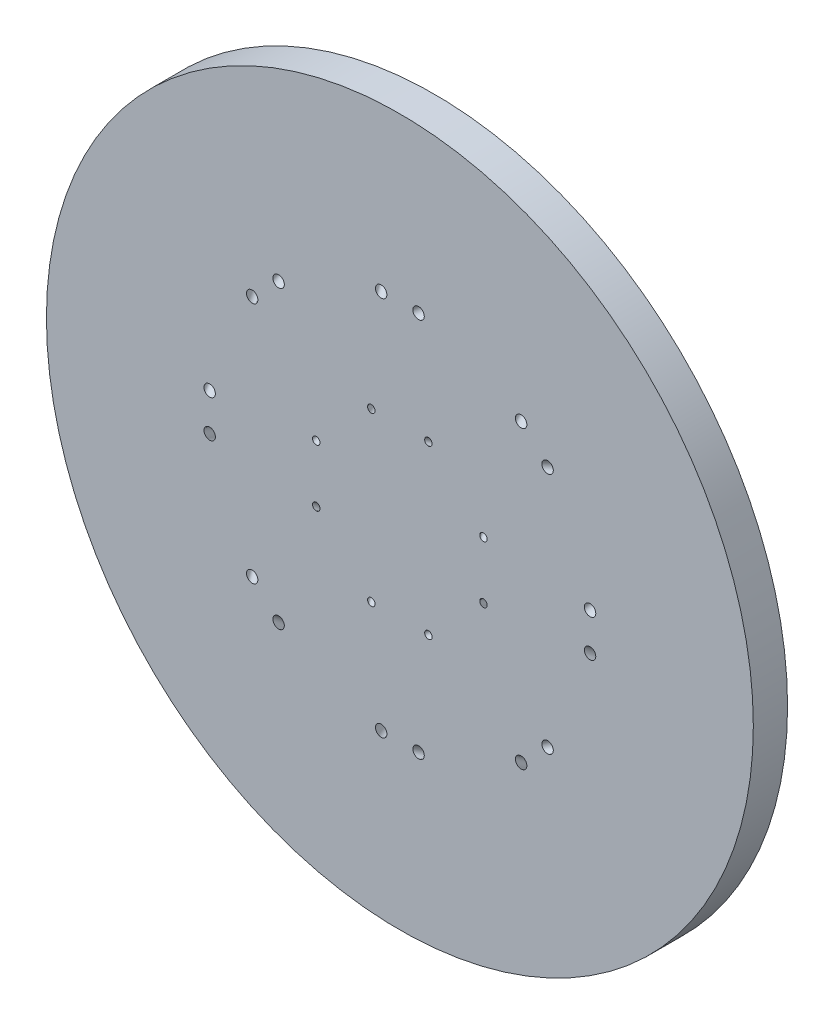
SolidWorks part; units mm, degrees
ref_plane "Front Plane" through (0, 0, 0) normal (0, 0, 1) x (1, 0, 0)
ref_plane "Top Plane" through (0, 0, 0) normal (0, 1, 0) x (1, 0, 0)
ref_plane "Right Plane" through (0, 0, 0) normal (1, 0, 0) x (0, 0, -1)
sketch "Sketch1" plane through (0, 0, 0) normal (0, 0, 1) x (1, 0, 0)
  circle A0 centre (0, 0) radius 38.1
  dimension "D1" = 76.2
extrude "Boss-Extrude1" add sketch "Sketch1" against normal blind 3.6912
sketch "Sketch2" plane through (0, 0, 0) normal (0, 0, 1) x (1, 0, 0)
  line L0 (0, 0) -> (0, 20.6) construction
  line L1 (0, 0) -> (20.6, 0) construction
  circle A0 centre (0, 0) radius 20.6 construction
  circle A1 centre (0, 0) radius 9.525 construction
  dimension "D1" = 41.2
  dimension "D2" = 19.05
sketch "Sketch4" plane through (0, 0, 0) normal (0, 0, 1) x (1, 0, 0)
  line L0 (-3.076, 9.0146) -> (3.076, 9.0146) construction
  line L1 (0, 0) -> (0, 20.6) construction
  line L3 (9.0146, 3.076) -> (9.0146, -3.076) construction
  line L4 (3.076, -9.0146) -> (-3.076, -9.0146) construction
  line L5 (-9.0146, -3.076) -> (-9.0146, 3.076) construction
  line L6 (-3.076, -9.0146) -> (3.076, -9.0146) construction
  line L8 (-9.0146, 3.076) -> (-9.0146, -3.076) construction
  circle A1 centre (9.0146, 3.076) radius 0.403
  circle A3 centre (-3.076, 9.0146) radius 0.403
  circle A4 centre (0, 0) radius 9.525 construction
  circle A5 centre (3.076, 9.0146) radius 0.403
  circle A6 centre (9.0146, -3.076) radius 0.403
  circle A7 centre (3.076, -9.0146) radius 0.403
  circle A8 centre (-3.076, -9.0146) radius 0.403
  circle A9 centre (-9.0146, -3.076) radius 0.403
  circle A10 centre (-9.0146, 3.076) radius 0.403
  point P6 (0, 9.0146)
  point P40 (0, 0)
  dimension "D1" = 0.806
  dimension "D2" = 0.806
  dimension "D3" = 6.152
  dimension "D4" = 4
sketch "Sketch5" plane through (0, 0, 0) normal (0, 0, 1) x (1, 0, 0)
  line L0 (-2.015, 20.5012) -> (2.015, 20.5012) construction
  line L1 (0, 0) -> (0, 20.6) construction
  line L2 (13.0717, 15.9214) -> (15.9214, 13.0717) construction
  line L3 (20.5012, -2.015) -> (20.5012, 2.015) construction
  line L4 (13.0717, -15.9214) -> (15.9214, -13.0717) construction
  line L5 (-2.015, -20.5012) -> (2.015, -20.5012) construction
  line L6 (-15.9214, -13.0717) -> (-13.0717, -15.9214) construction
  line L7 (-20.5012, 2.015) -> (-20.5012, -2.015) construction
  line L8 (-13.0717, 15.9214) -> (-15.9214, 13.0717) construction
  circle A0 centre (-2.015, 20.5012) radius 0.6152
  circle A1 centre (0, 0) radius 20.6 construction
  circle A2 centre (2.015, 20.5012) radius 0.6152
  circle A3 centre (13.0717, 15.9214) radius 0.6152
  circle A4 centre (15.9214, 13.0717) radius 0.6152
  circle A5 centre (20.5012, 2.015) radius 0.6152
  circle A6 centre (20.5012, -2.015) radius 0.6152
  circle A7 centre (15.9214, -13.0717) radius 0.6152
  circle A8 centre (13.0717, -15.9214) radius 0.6152
  circle A9 centre (2.015, -20.5012) radius 0.6152
  circle A10 centre (-2.015, -20.5012) radius 0.6152
  circle A11 centre (-13.0717, -15.9214) radius 0.6152
  circle A12 centre (-15.9214, -13.0717) radius 0.6152
  circle A13 centre (-20.5012, -2.015) radius 0.6152
  circle A14 centre (-20.5012, 2.015) radius 0.6152
  circle A15 centre (-15.9214, 13.0717) radius 0.6152
  circle A16 centre (-13.0717, 15.9214) radius 0.6152
  point P6 (0, 20.5012)
  point P28 (0, 0)
  dimension "D1" = 1.2304
  dimension "D2" = 1.2304
  dimension "D3" = 4.03
  dimension "D4" = 8
ref_plane "Plane1" through (0, 17.9868, 6.725) normal (0, 0.9367, 0.3502) x (1, 0, 0)
ref_plane "Plane2" through (0, 7.909, -2.9571) normal (0, -0.9367, 0.3502) x (1, 0, 0)
ref_plane "Plane3" through (12.7186, 12.7186, 6.725) normal (0.6623, 0.6623, 0.3502) x (0.7071, -0.7071, 0)
ref_plane "Plane4" through (17.9868, 0, 6.725) normal (0.9367, 0, 0.3502) x (0, 1, 0)
ref_plane "Plane5" through (12.7186, -12.7186, 6.725) normal (0.6623, -0.6623, 0.3502) x (0.7071, 0.7071, 0)
ref_plane "Plane7" through (-7.909, 0, -2.9571) normal (0.9367, 0, 0.3502) x (0, -1, 0)
ref_plane "Plane8" through (0, -7.909, -2.9571) normal (0, 0.9367, 0.3502) x (-1, 0, 0)
ref_plane "Plane9" through (0, -7.909, -2.9571) normal (0, 0.9367, 0.3502) x (1, 0, 0)
ref_plane "Plane10" through (-12.7186, -12.7186, 6.725) normal (-0.6623, -0.6623, 0.3502) x (0.7071, -0.7071, 0)
ref_plane "Plane11" through (-7.909, 0, 2.9571) normal (-0.9367, 0, 0.3502) x (0, 1, 0)
ref_plane "Plane12" through (7.909, 0, -2.9571) normal (-0.9367, 0, 0.3502) x (0, -1, 0)
ref_plane "Plane13" through (-12.7186, 12.7186, 6.725) normal (-0.6623, 0.6623, 0.3502) x (-0.7071, -0.7071, 0)
ref_plane "Plane14" through (0, -17.9868, 6.725) normal (0, -0.9367, 0.3502) x (1, 0, 0)
sketch "Sketch6" plane through (12.7186, -12.7186, 6.725) normal (0.6623, -0.6623, 0.3502) x (0.7071, 0.7071, 0)
  line L0 (-2.015, -7.1797) -> (2.015, -7.1797)
  line L1 (0, -7.1797) -> (0, -3.6896) construction
  line L2 (-2.015, -7.1797) -> (0, -3.6896)
  line L3 (0, -3.6896) -> (2.015, -7.1797)
  dimension "D1" = 60
sketch "Sketch7" plane through (17.9868, 0, 6.725) normal (0.9367, 0, 0.3502) x (0, 1, 0)
  line L0 (-2.015, -7.1797) -> (2.015, -7.1797)
  line L1 (0, -7.1797) -> (0, -3.6896) construction
  line L2 (-2.015, -7.1797) -> (0, -3.6896)
  line L3 (0, -3.6896) -> (2.015, -7.1797)
  dimension "D1" = 60
sketch "Sketch8" plane through (12.7186, 12.7186, 6.725) normal (0.6623, 0.6623, 0.3502) x (0.7071, -0.7071, 0)
  line L0 (-2.015, 7.1797) -> (2.015, 7.1797)
  line L1 (0, 7.1797) -> (0, 3.6896) construction
  line L3 (-2.015, 7.1797) -> (0, 3.6896)
  line L4 (0, 3.6896) -> (2.015, 7.1797)
  dimension "D1" = 60
sketch "Sketch9" plane through (0, 17.9868, 6.725) normal (0, 0.9367, 0.3502) x (1, 0, 0)
  line L0 (-2.015, 7.1797) -> (2.015, 7.1797)
  line L1 (0, 7.1797) -> (0, 3.6896) construction
  line L2 (0, 0) -> (0, 7.2143) construction
  line L3 (-2.015, 7.1797) -> (0, 3.6896)
  line L4 (0, 3.6896) -> (2.015, 7.1797)
  dimension "D1" = 60
sketch "Sketch10" plane through (0, 7.909, -2.9571) normal (0, -0.9367, 0.3502) x (1, 0, 0)
  line L0 (-3.076, 3.157) -> (3.076, 3.157)
  line L1 (0, 3.157) -> (0, 8.4848) construction
  line L2 (0, 0) -> (0, 7.2143) construction
  line L3 (0, 8.4848) -> (-3.076, 3.157)
  line L4 (0, 8.4848) -> (3.076, 3.157)
  dimension "D1" = 60
sketch "Sketch12" plane through (-7.909, 0, -2.9571) normal (0.9367, 0, 0.3502) x (0, -1, 0)
  line L0 (-3.076, -3.157) -> (3.076, -3.157)
  line L1 (0, -3.157) -> (0, -8.4848) construction
  line L2 (-3.076, -3.157) -> (0, -8.4848)
  line L3 (0, -8.4848) -> (3.076, -3.157)
  dimension "D1" = 60
sketch "Sketch14" plane through (0, -7.909, -2.9571) normal (0, 0.9367, 0.3502) x (1, 0, 0)
  line L0 (-3.076, -3.157) -> (3.076, -3.157)
  line L1 (0, -3.157) -> (0, -8.4848) construction
  line L2 (-3.076, -3.157) -> (0, -8.4848)
  line L3 (0, -8.4848) -> (3.076, -3.157)
  dimension "D1" = 60
ref_plane "Plane15" through (-17.9868, 0, 6.725) normal (-0.9367, 0, 0.3502) x (0, -1, 0)
sketch "Sketch16" plane through (7.909, 0, -2.9571) normal (-0.9367, 0, 0.3502) x (0, -1, 0)
  line L0 (-3.076, 3.157) -> (3.076, 3.157)
  line L4 (-3.076, 3.157) -> (0, 8.4848)
  line L5 (0, 8.4848) -> (3.076, 3.157)
  line L6 (0, 3.157) -> (0, 8.4848) construction
  dimension "D2" = 60
sketch "Sketch17" plane through (0, -7.909, -2.9571) normal (0, 0.9367, 0.3502) x (-1, 0, 0)
  line L0 (-3.076, 3.157) -> (3.076, 3.157)
  line L1 (0, 3.157) -> (0, 8.4848) construction
  line L3 (-3.076, 3.157) -> (0, 8.4848)
  line L4 (0, 8.4848) -> (3.076, 3.157)
  dimension "D1" = 60
sketch "Sketch18" plane through (0, 17.9868, 6.725) normal (0, 0.9367, 0.3502) x (1, 0, 0)
  line L0 (0, 10.3969) -> (0, -5.2208) construction
sketch "Sketch20" plane through (0, 7.909, -2.9571) normal (0, -0.9367, 0.3502) x (1, 0, 0)
  line L0 (0, 3.157) -> (0, 18.139) construction
sketch "Sketch21" plane through (-12.7186, -12.7186, 6.725) normal (-0.6623, -0.6623, 0.3502) x (0.7071, -0.7071, 0)
  line L0 (-2.015, -7.1797) -> (2.015, -7.1797)
  line L1 (2.015, -7.1797) -> (0, -3.6896)
  line L2 (0, -3.6896) -> (-2.015, -7.1797)
  line L3 (0, -7.1797) -> (0, -3.6896) construction
  dimension "D1" = 60
sketch "Sketch22" plane through (-12.7186, 12.7186, 6.725) normal (-0.6623, 0.6623, 0.3502) x (-0.7071, -0.7071, 0)
  line L0 (2.015, -7.1797) -> (-2.015, -7.1797)
  line L1 (-2.015, -7.1797) -> (0, -3.6896)
  line L2 (0, -3.6896) -> (2.015, -7.1797)
  line L3 (0, -7.1797) -> (0, -3.6896) construction
  dimension "D1" = 60
sketch "Sketch23" plane through (0, -17.9868, 6.725) normal (0, -0.9367, 0.3502) x (1, 0, 0)
  line L0 (-2.015, -7.1797) -> (2.015, -7.1797)
  line L1 (2.015, -7.1797) -> (0, -3.6896)
  line L2 (0, -3.6896) -> (-2.015, -7.1797)
  line L3 (0, -3.6896) -> (0, -7.1797) construction
  dimension "D1" = 60
sketch "Sketch24" plane through (-17.9868, 0, 6.725) normal (-0.9367, 0, 0.3502) x (0, -1, 0)
  line L0 (-2.015, -7.1797) -> (2.015, -7.1797)
  line L1 (2.015, -7.1797) -> (0, -3.6896)
  line L2 (0, -3.6896) -> (-2.015, -7.1797)
  line L3 (0, -3.6896) -> (0, -7.1797) construction
  dimension "D1" = 60
extrude "Cut-Extrude1" cut sketch "Sketch5" along direction (0.5, -0.3033, 0.8112) on the side against the normal up to surface (3.6912 mm away) contours A0 up to face at (38.1, 0, -3.6912)
extrude "Cut-Extrude2" cut sketch "Sketch5<3>" along direction (0.5, 0.3033, -0.8112) on the side against the normal up to surface (3.6912 mm away) contours A2 region at (2.015, 20.5012, 0) up to face at (-4.9032, 21.8293, -3.6912)
sketch "Sketch5<3>" plane through (0, 0, 0) normal (0, 0, 1) x (1, 0, 0) same geometry as "Sketch5"
extrude "Cut-Extrude3" cut sketch "Sketch5<4>" along direction (0.1391, -0.568, 0.8112) on the side against the normal up to surface (3.6912 mm away) contours A3 region at (13.0717, 15.9214, 0) up to face at (3.6772, 21.8293, -3.6912)
sketch "Sketch5<4>" plane through (0, 0, 0) normal (0, 0, 1) x (1, 0, 0) same geometry as "Sketch5"
extrude "Cut-Extrude4" cut sketch "Sketch5<5>" along direction (0.568, -0.1391, -0.8112) on the side against the normal up to surface (3.6912 mm away) contours A4 region at (15.9214, 13.0717, 0) up to face at (11.8258, 18.454, -3.6912)
sketch "Sketch5<5>" plane through (0, 0, 0) normal (0, 0, 1) x (1, 0, 0) same geometry as "Sketch5"
extrude "Cut-Extrude5" cut sketch "Sketch5<6>" along direction (-0.3033, 0.5, 0.8112) on the side against the normal up to surface (3.6912 mm away) contours A6 region at (20.5012, -2.015, 0) up to face at (17.893, 12.3868, -3.6912)
sketch "Sketch5<6>" plane through (0, 0, 0) normal (0, 0, 1) x (1, 0, 0) same geometry as "Sketch5"
extrude "Cut-Extrude6" cut sketch "Sketch5<7>" along direction (0.3033, 0.5, -0.8112) on the side against the normal up to surface (3.6912 mm away) contours A5 region at (20.5012, 2.015, 0) up to face at (21.2683, -4.3422, -3.6912)
sketch "Sketch5<7>" plane through (0, 0, 0) normal (0, 0, 1) x (1, 0, 0) same geometry as "Sketch5"
extrude "Cut-Extrude7" cut sketch "Sketch5<8>" along direction (0.1391, 0.568, 0.8112) on the side against the normal up to surface (3.6912 mm away) contours A8 region at (13.0717, -15.9214, 0) up to face at (21.2683, 4.2382, -3.6912)
sketch "Sketch5<8>" plane through (0, 0, 0) normal (0, 0, 1) x (1, 0, 0) same geometry as "Sketch5"
extrude "Cut-Extrude8" cut sketch "Sketch5<9>" along direction (0.568, 0.1391, -0.8112) on the side against the normal up to surface (3.6912 mm away) contours A7 region at (15.9214, -13.0717, 0) up to face at (11.8258, -18.5581, -3.6912)
sketch "Sketch5<9>" plane through (0, 0, 0) normal (0, 0, 1) x (1, 0, 0) same geometry as "Sketch5"
extrude "Cut-Extrude9" cut sketch "Sketch4" along direction (-0.5, -0.3033, -0.8112) on the side against the normal up to surface (3.6912 mm away) contours A3 region at (-3.076, 9.0146, 0) up to face at (17.893, -12.4908, -3.6912)
extrude "Cut-Extrude10" cut sketch "Sketch4<3>" along direction (0.5, -0.3033, -0.8112) on the side against the normal up to surface (3.6912 mm away) contours A5 region at (3.076, 9.0146, 0) up to face at (-5.7528, 7.6005, -3.6912)
sketch "Sketch4<3>" plane through (0, 0, 0) normal (0, 0, 1) x (1, 0, 0) same geometry as "Sketch4"
extrude "Cut-Extrude11" cut sketch "Sketch4<4>" along direction (0.5, -0.3033, 0.8112) on the side against the normal up to surface (3.6912 mm away) contours A8 region at (-3.076, -9.0146, 0) up to face at (4.9496, 7.6005, -3.6912)
sketch "Sketch4<4>" plane through (0, 0, 0) normal (0, 0, 1) x (1, 0, 0) same geometry as "Sketch4"
extrude "Cut-Extrude12" cut sketch "Sketch4<6>" along direction (0.5, 0.3033, -0.8112) on the side against the normal up to surface (3.6912 mm away) contours A7 region at (3.076, -9.0146, 0) up to face at (-5.7528, -7.6686, -3.6912)
sketch "Sketch4<6>" plane through (0, 0, 0) normal (0, 0, 1) x (1, 0, 0) same geometry as "Sketch4"
extrude "Cut-Extrude13" cut sketch "Sketch4<7>" along direction (-0.3033, -0.5, 0.8112) on the side against the normal up to surface (3.6912 mm away) contours A10 region at (-9.0146, 3.076, 0) up to face at (4.9496, -7.6686, -3.6912)
sketch "Sketch4<7>" plane through (0, 0, 0) normal (0, 0, 1) x (1, 0, 0) same geometry as "Sketch4"
extrude "Cut-Extrude14" cut sketch "Sketch4<8>" along direction (0.3033, -0.5, -0.8112) on the side against the normal up to surface (3.6912 mm away) contours A9 region at (-9.0146, -3.076, 0) up to face at (-8.0361, 5.3171, -3.6912)
sketch "Sketch4<8>" plane through (0, 0, 0) normal (0, 0, 1) x (1, 0, 0) same geometry as "Sketch4"
extrude "Cut-Extrude26" cut sketch "Sketch5<10>" along direction (-0.5, 0.3033, 0.8112) on the side against the normal up to surface (3.6912 mm away) contours A9 region at (2.015, -20.5012, 0) up to face at (-8.0361, -5.3853, -3.6912)
sketch "Sketch5<10>" plane through (0, 0, 0) normal (0, 0, 1) x (1, 0, 0) same geometry as "Sketch5"
extrude "Cut-Extrude27" cut sketch "Sketch5<11>" along direction (-0.5, -0.3033, -0.8112) on the side against the normal up to surface (3.6912 mm away) contours A10 region at (-2.015, -20.5012, 0) up to face at (3.6772, -21.9333, -3.6912)
sketch "Sketch5<11>" plane through (0, 0, 0) normal (0, 0, 1) x (1, 0, 0) same geometry as "Sketch5"
extrude "Cut-Extrude28" cut sketch "Sketch5<12>" along direction (-0.1391, 0.568, 0.8112) on the side against the normal up to surface (3.6912 mm away) contours A11 region at (-13.0717, -15.9214, 0) up to face at (-4.9032, -21.9333, -3.6912)
sketch "Sketch5<12>" plane through (0, 0, 0) normal (0, 0, 1) x (1, 0, 0) same geometry as "Sketch5"
extrude "Cut-Extrude29" cut sketch "Sketch5<13>" along direction (-0.568, 0.1391, -0.8112) on the side against the normal up to surface (3.6912 mm away) contours A12 region at (-15.9214, -13.0717, 0) up to face at (-13.0518, -18.5581, -3.6912)
sketch "Sketch5<13>" plane through (0, 0, 0) normal (0, 0, 1) x (1, 0, 0) same geometry as "Sketch5"
extrude "Cut-Extrude30" cut sketch "Sketch5<14>" along direction (0.3033, 0.5, 0.8112) on the side against the normal up to surface (3.6912 mm away) contours A13 region at (-20.5012, -2.015, 0) up to face at (-19.119, -12.4908, -3.6912)
sketch "Sketch5<14>" plane through (0, 0, 0) normal (0, 0, 1) x (1, 0, 0) same geometry as "Sketch5"
extrude "Cut-Extrude31" cut sketch "Sketch5<15>" along direction (-0.3033, 0.5, -0.8112) on the side against the normal up to surface (3.6912 mm away) contours A14 region at (-20.5012, 2.015, 0) up to face at (-22.4943, -4.3422, -3.6912)
sketch "Sketch5<15>" plane through (0, 0, 0) normal (0, 0, 1) x (1, 0, 0) same geometry as "Sketch5"
extrude "Cut-Extrude32" cut sketch "Sketch5<16>" along direction (-0.568, -0.1391, -0.8112) on the side against the normal up to surface (3.6912 mm away) contours A15 region at (-15.9214, 13.0717, 0) up to face at (-22.4943, 4.2382, -3.6912)
sketch "Sketch5<16>" plane through (0, 0, 0) normal (0, 0, 1) x (1, 0, 0) same geometry as "Sketch5"
extrude "Cut-Extrude33" cut sketch "Sketch5<17>" along direction (-0.1391, -0.568, 0.8112) on the side against the normal up to surface (3.6912 mm away) contours A16 region at (-13.0717, 15.9214, 0) up to face at (-19.119, 12.3868, -3.6912)
sketch "Sketch5<17>" plane through (0, 0, 0) normal (0, 0, 1) x (1, 0, 0) same geometry as "Sketch5"
extrude "Cut-Extrude34" cut sketch "Sketch4<20>" along direction (-0.3033, -0.5, -0.8112) on the side against the normal up to surface (3.6912 mm away) contours A6 region at (9.0146, -3.076, 0) up to face at (-13.0518, 18.454, -3.6912)
sketch "Sketch4<20>" plane through (0, 0, 0) normal (0, 0, 1) x (1, 0, 0) same geometry as "Sketch4"
extrude "Cut-Extrude35" cut sketch "Sketch4<21>" along direction (0.3033, -0.5, 0.8112) on the side against the normal up to surface (3.6912 mm away) contours A1 region at (9.0146, 3.076, 0) up to face at (7.233, -5.3853, -3.6912)
sketch "Sketch4<21>" plane through (0, 0, 0) normal (0, 0, 1) x (1, 0, 0) same geometry as "Sketch4"
equation "\"PLATE DIAMETER\"= 0.0762"
equation "\"FUEL ORIFICE DIAMETER\"= 0.000805996"
equation "\"OXIDIZER ORIFICE DIAMETER\"= 0.0012304"
equation "\"IMPINGE ANGLE\"= 60"
equation "\"FUEL ORIFICE LENGTH\"= 0.00241799"
equation "\"OXIDIZER ORIFICE LENGTH\"= 0.0036912"
equation "\"FUEL JET LENGTH\"= 0.00402998"
equation "\"OXIDIZER JET LENGTH\"= 0.006152"
equation "\"D1@Sketch1\"=\"PLATE DIAMETER\""
equation "\"D1@Boss-Extrude1\"=\"OXIDIZER ORIFICE LENGTH\""
equation "\"D1@Sketch2\"=\"PLATE DIAMETER\"-0.035"
equation "\"D2@Sketch2\"=\"PLATE DIAMETER\"/4"
equation "\"D1@Sketch4\"=\"FUEL ORIFICE DIAMETER\""
equation "\"D2@Sketch4\"=\"FUEL ORIFICE DIAMETER\""
equation "\"D3@Sketch4\"=\"OXIDIZER JET LENGTH\""
equation "\"D1@Sketch5\"=\"OXIDIZER ORIFICE DIAMETER\""
equation "\"D2@Sketch5\"=\"OXIDIZER ORIFICE DIAMETER\""
equation "\"D3@Sketch5\"=\"FUEL JET LENGTH\""
equation "\"D1@Sketch6\"=\"IMPINGE ANGLE\""
equation "\"D1@Sketch7\"=\"IMPINGE ANGLE\""
equation "\"D1@Sketch8\"=\"IMPINGE ANGLE\""
equation "\"D1@Sketch9\"=\"IMPINGE ANGLE\""
equation "\"D1@Sketch10\"=\"IMPINGE ANGLE\""
equation "\"D1@Sketch12\"=\"IMPINGE ANGLE\""
equation "\"D1@Sketch14\"=\"IMPINGE ANGLE\""
equation "\"D1@Sketch17\"=\"IMPINGE ANGLE\""
equation "\"D2@Sketch16\"=\"IMPINGE ANGLE\""
equation "\"D1@Sketch21\"=\"IMPINGE ANGLE\""
equation "\"D1@Sketch22\"=\"IMPINGE ANGLE\""
equation "\"D1@Sketch23\"=\"IMPINGE ANGLE\""
equation "\"D1@Sketch24\"=\"IMPINGE ANGLE\""
